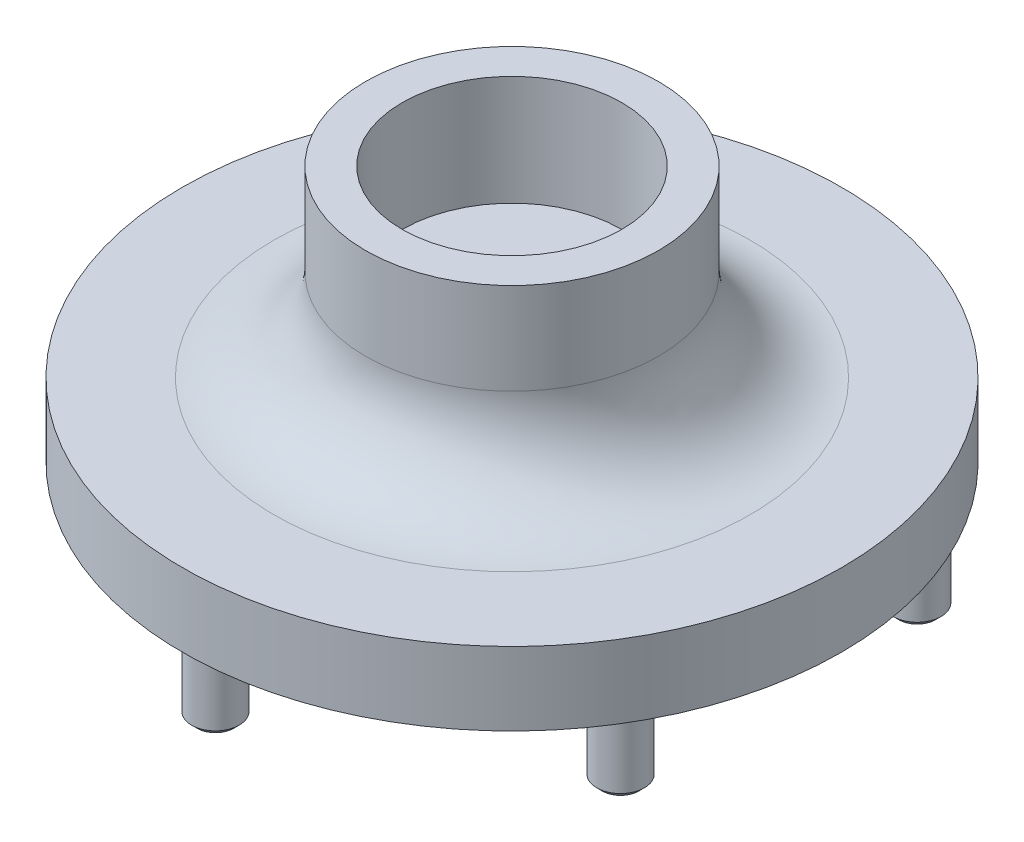
SolidWorks part; units mm, degrees
ref_plane "Front Plane" through (0, 0, 0) normal (0, 0, 1) x (1, 0, 0)
ref_plane "Top Plane" through (0, 0, 0) normal (0, 1, 0) x (1, 0, 0)
ref_plane "Right Plane" through (0, 0, 0) normal (1, 0, 0) x (0, 0, -1)
sketch "Sketch1" plane through (0, 0, 0) normal (0, 0, 1) x (1, 0, 0)
  line L0 (0, 0) -> (-30, 0)
  line L1 (-30, 0) -> (-30, 30)
  line L2 (-30, 30) -> (-50, 30)
  line L3 (-50, 30) -> (-50, 35)
  line L4 (-50, 35) -> (-90, 35)
  line L5 (-90, 35) -> (-90, 55)
  line L6 (-90, 55) -> (-40, 55)
  line L7 (-40, 55) -> (-40, 105)
  line L8 (-40, 105) -> (-30, 105)
  line L9 (-30, 105) -> (-30, 75)
  line L10 (-30, 75) -> (0, 75)
  line L11 (0, 75) -> (0, 0)
  dimension "D1" = 30
  dimension "D2" = 30
  dimension "D3" = 20
  dimension "D4" = 40
  dimension "D5" = 50
  dimension "D6" = 50
  dimension "D7" = 10
  dimension "D8" = 30
  dimension "D9" = 75
  dimension "D10" = 30
revolve "Revolve1" add sketch "Sketch1" angle 360 about L11
sketch "Sketch2" plane through (0, 55, 0) normal (0, 1, 0) x (1, 0, 0)
  circle A0 centre (0, 81) radius 6.5
  dimension "D1" = 13
  dimension "D2" = 81
extrude "Boss-Extrude1" add sketch "Sketch2" against normal blind 40
pattern_circular "CirPattern1" count 6 over 360 about axis through (0, 55, 0) along (0, 1, 0) of "Boss-Extrude1"
chamfer "Chamfer1" distance 1.5 angle 45 6 edges at (66.8981, 15, -46.1292) (73.3981, 15, 34.8708) (6.5, 15, 81) (-66.8981, 15, 46.1292) (-73.3981, 15, -34.8708) (-6.5, 15, -81)
fillet "Fillet1" radius 25 2 edges at (-30, 30, 0) (-40, 55, 0)
fillet "Fillet2" radius 15 1 edges at (-30, 0, 0)
